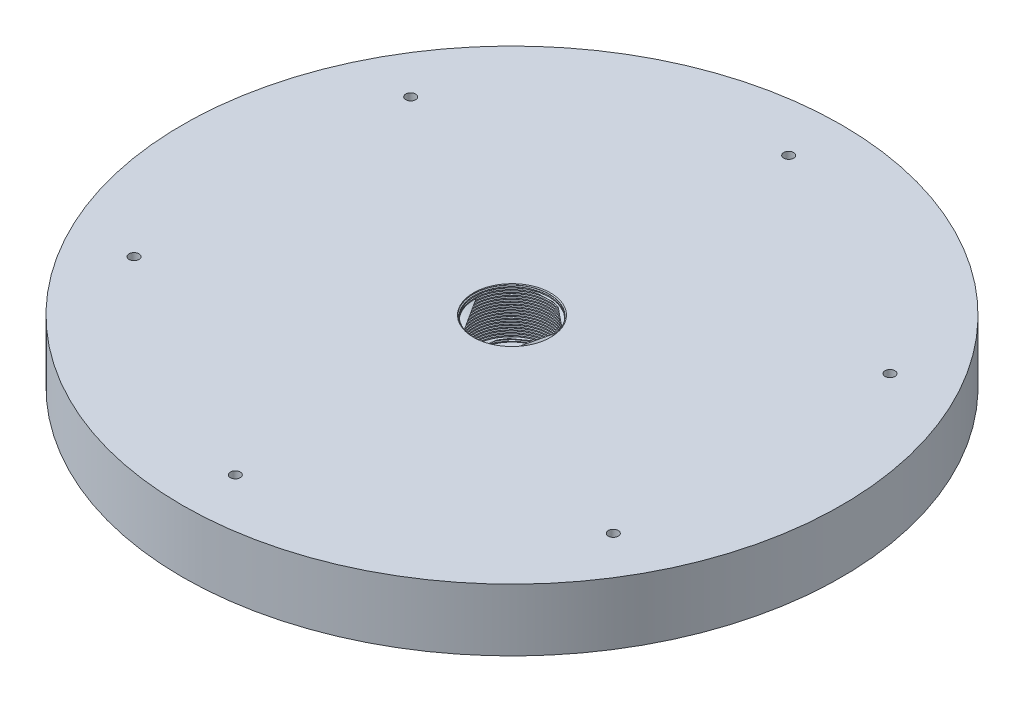
SolidWorks part; units mm, degrees
material "1023 Carbon Steel Sheet (SS)"
ref_plane "Front Plane" through (0, 0, 0) normal (0, 0, 1) x (1, 0, 0)
ref_plane "Top Plane" through (0, 0, 0) normal (0, 1, 0) x (1, 0, 0)
ref_plane "Right Plane" through (0, 0, 0) normal (1, 0, 0) x (0, 0, -1)
sketch "Sketch1" plane through (0, 0, 0) normal (0, 1, 0) x (1, 0, 0)
  line L0 (0, 0) -> (0, 348.7265) construction
  line L1 (0, 0) -> (192.6907, 111.25) construction
  circle A21 centre (0, 0) radius 265
  circle A22 centre (0, 0) radius 222.5 construction
  circle A23 centre (0, 222.5) radius 4
  circle A24 centre (192.6907, 111.25) radius 4
  circle A25 centre (192.6907, -111.25) radius 4
  circle A26 centre (0, -222.5) radius 4
  circle A27 centre (-192.6907, -111.25) radius 4
  circle A28 centre (-192.6907, 111.25) radius 4
  point P6 (0, 0)
  point P7 (0, 0)
  point P18 (0, 0)
  point P19 (0, 0)
  dimension "D2" = 222.5
  dimension "D3" = 8
  dimension "D1" = 530
  dimension "D4" = 6
extrude "Boss-Extrude1" add sketch "Sketch1" along normal mid plane 50
sketch "Sketch2" plane through (0, 25, 0) normal (0, 1, 0) x (1, 0, 0)
  circle A0 centre (0, 0) radius 30
  dimension "D1" = 60
extrude "Cut-Extrude1" cut sketch "Sketch2" against normal blind 40
chamfer "Chamfer1" distance 1 angle 45 1 edges at (0, 25, 30)
thread "Thread1" pitch 1.5 method cut profile "Thread Profile1" start angle 0, offset 5, length 0, pitch 2, diameter 60
ref_plane "Plane1" through (-30, 29, 0) normal (0, 0, 1) x (-1, 0, 0)
sketch "Thread Profile1" plane through (-30, 29, 0) normal (0, 0, 1) x (-1, 0, 0)
  line L0 (0, 0) -> (0, 1.5) construction
  line L1 (0, 0) -> (0.8119, 0.4687)
  line L2 (0.8119, 0.4687) -> (0.8119, 0.6562)
  line L3 (0.8119, 0.6562) -> (0, 1.125)
  line L4 (0.8119, 0.5625) -> (0, 0.5625) construction
  line L11 (0, 0) -> (0, 1.125)
  point P2 (0, 0)
  dimension "Pitch" = 1.5
  dimension "Profile_Angle" = 60
  dimension "Profile_Land" = 0.1875
  dimension "Profile_Height" = 0.8119
sketch "Sketch3" plane through (0, -25, 0) normal (0, -1, 0) x (1, 0, 0)
  circle A0 centre (0, 0) radius 265
extrude "Boss-Extrude2" add sketch "Sketch3" against normal blind 10
